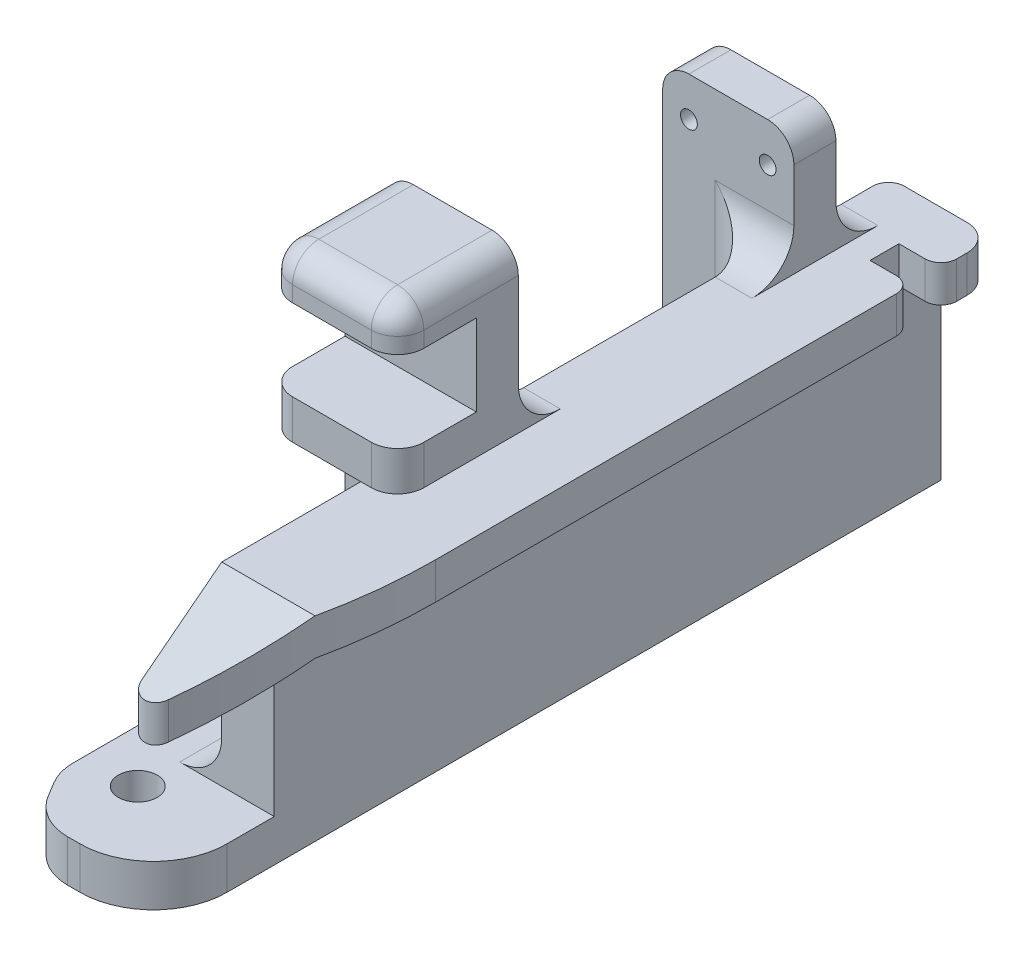
SolidWorks part; units mm, degrees
ref_plane "Front Plane" through (0, 0, 0) normal (0, 0, 1) x (1, 0, 0)
ref_plane "Top Plane" through (0, 0, 0) normal (0, 1, 0) x (1, 0, 0)
ref_plane "Right Plane" through (0, 0, 0) normal (1, 0, 0) x (0, 0, -1)
sketch "Sketch1" plane through (0, 0, 0) normal (0, 1, 0) x (1, 0, 0)
  line L6 (0, 0) -> (0, -140)
  line L13 (0, 0) -> (28, 0)
  line L14 (28, 0) -> (28, -135.9955)
  line L16 (0, -140) -> (6, -150)
  line L17 (6, -150) -> (13.9955, -150)
  circle A1 centre (10, -135) radius 3.7
  arc A2 (13.9955, -150) -> (28, -135.9955) centre (13.9955, -135.9955) ccw
  dimension "D12" = 7.4
  dimension "D2" = 7.9955
  dimension "D3" = 6
  dimension "D4" = 150
  dimension "D5" = 28
  dimension "D6" = 10
  dimension "D7" = 15
  dimension "D8" = 10
extrude "Boss-Extrude1" add sketch "Sketch1" along normal blind 8
fillet "Fillet1" radius 10 2 edges at (0, 4, 140) (6, 4, 150)
sketch "Sketch2" plane through (0, 8, 0) normal (0, 1, 0) x (1, 0, 0)
  line L0 (28, -127) -> (28, 0)
  line L1 (-55, 0) -> (55, 0) construction
  line L2 (28, -135.9955) -> (28, 0) construction
  line L3 (28, 0) -> (18, 0)
  line L4 (18, 0) -> (18, -127)
  line L6 (18, -127) -> (28, -127)
  circle A2 centre (10, -135) radius 3.7 construction
  dimension "D1" = 10
  dimension "D2" = 8
extrude "Boss-Extrude2" add sketch "Sketch2" along normal blind 30 contours L4 L6 L0 L3
sketch "Sketch3" plane through (0, 38, 0) normal (0, 1, 0) x (1, 0, 0)
  line L0 (18, 0) -> (38, 0)
  line L1 (-4.4, 0) -> (4.4, 0) construction
  line L2 (18, 0) -> (18, -127) construction
  line L3 (38, 0) -> (38, -106.265)
  line L4 (18, 0) -> (18, -127)
  line L5 (18, -127) -> (25, -155)
  line L6 (18, 0) -> (18, -127) construction
  line L7 (11.6619, -150) -> (13.9955, -150) construction
  arc A0 (38, -106.265) -> (25, -155) centre (-59.85, -106.265) cw
  circle A4 centre (10, -135) radius 3.7 construction
  dimension "D2" = 5
  dimension "D1" = 20
  dimension "D3" = 15
extrude "Boss-Extrude3" add sketch "Sketch3" along normal blind 7
fillet "Fillet2" radius 3 3 edges at (0, 4, 0) (18, 26.5, 0) (25, 41.5, 155)
sketch "Sketch4" plane through (0, 8, 0) normal (0, 1, 0) x (1, 0, 0)
  line L0 (0, -4.4) -> (0, 4.4) construction
  line L1 (0, -17.0103) -> (18, -17.0103)
  line L2 (0, -17.0103) -> (0, -25.0103)
  line L3 (0, -25.0103) -> (18, -25.0103)
  line L4 (18, -17.0103) -> (18, -25.0103)
  line L5 (18, -3) -> (18, -127) construction
  line L6 (18, -3) -> (18, -127) construction
  line L7 (0, -77.5073) -> (18, -77.5073)
  line L8 (0, -77.5073) -> (0, -85.5073)
  line L9 (0, -85.5073) -> (18, -85.5073)
  line L10 (18, -77.5073) -> (18, -85.5073)
  line L11 (0, -3) -> (0, -137.2302) construction
  line L13 (-101.25, -25.5103) -> (121.25, -25.5103) construction
  line L15 (-101.25, -85.5073) -> (121.25, -85.5073) construction
  dimension "D1" = 8
  dimension "D2" = 8
  dimension "D3" = 0.5
extrude "Boss-Extrude4" add sketch "Sketch4" along normal blind 27
sketch "Sketch5" plane through (0, 35, 0) normal (0, 1, 0) x (1, 0, 0)
  line L1 (0, -17.0103) -> (25, -17.0103)
  line L2 (0, -17.0103) -> (0, -25.0103)
  line L3 (0, -25.0103) -> (25, -25.0103)
  line L4 (25, -17.0103) -> (25, -25.0103)
  line L5 (0, -85.5073) -> (25, -85.5073)
  line L6 (0, -85.5073) -> (0, -77.5073)
  line L7 (0, -77.5073) -> (25, -77.5073)
  line L8 (25, -85.5073) -> (25, -77.5073)
  dimension "D1" = 25
  dimension "D2" = 25
extrude "Boss-Extrude5" add sketch "Sketch5" along normal blind 33
sketch "Sketch6" plane through (0, 68, 0) normal (0, 1, 0) x (1, 0, 0)
  line L0 (0, -85.5073) -> (0, -137.2302) construction
  line L1 (25, -77.5073) -> (0, -77.5073)
  line L2 (25, -77.5073) -> (25, -100.513)
  line L3 (25, -100.513) -> (0, -100.513)
  line L4 (0, -77.5073) -> (0, -100.513)
  dimension "D1" = 23.0057
extrude "Boss-Extrude6" add sketch "Sketch6" along normal blind 8
sketch "Sketch7" plane through (0, 0, 85.5073) normal (0, 0, 1) x (1, 0, 0)
  line L0 (0, 68) -> (0, 8) construction
  line L1 (0, 45) -> (25, 45)
  line L2 (0, 45) -> (0, 52.5)
  line L3 (0, 52.5) -> (25, 52.5)
  line L4 (25, 45) -> (25, 52.5)
  line L5 (25, 68) -> (25, 45) construction
  line L6 (0, 76) -> (25, 76) construction
  line L7 (28.7089, 45) -> (23.0833, 45) construction
  dimension "D1" = 23.5
extrude "Boss-Extrude7" add sketch "Sketch7" along normal blind 15
sketch "Sketch8" plane through (0, 0, 17.0103) normal (0, 0, -1) x (-1, 0, 0)
  line L0 (-25, 68) -> (0, 68) construction
  line L1 (-25, 68) -> (-25, 45) construction
  line L2 (0, 68) -> (0, 8) construction
  circle A0 centre (-20, 60.5) radius 1.6
  circle A1 centre (-5, 60.5) radius 1.6
  dimension "D1" = 3.2
  dimension "D2" = 3.2
  dimension "D3" = 7.5
  dimension "D4" = 5
  dimension "D5" = 5
extrude "Cut-Extrude1" cut sketch "Sketch8" against normal up to next
fillet "Fillet3" radius 8 14 edges at (18.8787, 8, 0.8787) (18, 8, 51.2588) (18, 8, 106.2536) (9, 8, 17.0103) (18, 26.5, 17.0103) (18, 26.5, 25.0103) (9, 8, 25.0103) (9, 8, 77.5073) (18, 26.5, 77.5073) (18, 26.5, 85.5073) (9, 8, 85.5073) (21.5, 45, 25.0103) (21.5, 45, 77.5073) (21.5, 45, 17.0103)
fillet "Fillet4" radius 5 10 edges at (38, 41.5, 0) (25, 68, 21.0103) (25, 76, 89.0101) (0, 76, 89.0101) (0, 68, 21.0103) (12.5, 76, 100.513) (25, 72, 100.513) (0, 72, 100.513) (25, 48.75, 100.5073) (0, 48.75, 100.5073)
sketch "Sketch9" plane through (0, 45, 0) normal (0, 1, 0) x (1, 0, 0)
  line L0 (38, -106.265) -> (38, -5) construction
  line L1 (38, -15.5041) -> (30, -15.5041)
  line L2 (38, -15.5041) -> (38, -10.0041)
  line L3 (38, -10.0041) -> (30, -10.0041)
  line L4 (30, -15.5041) -> (30, -10.0041)
  line L5 (71.25, -15.5041) -> (91.25, -15.5041) construction
  dimension "D1" = 8
  dimension "D2" = 5.5
extrude "Cut-Extrude2" cut sketch "Sketch9" against normal up to next
fillet "Fillet7" radius 3 2 edges at (38, 41.5, 15.5041) (38, 41.5, 10.0041)
sketch "Sketch10" plane through (0, 38, 0) normal (0, -1, 0) x (1, 0, 0)
  line L0 (18, 127) -> (28, 127) construction
  line L1 (18, 127) -> (23.0833, 147.3333) construction
  line L2 (18, 127) -> (28, 127)
  line L3 (18, 127) -> (23.0833, 147.3333)
  line L4 (28, 127) -> (35.7778, 127)
  arc A0 (28.7089, 147.8816) -> (23.0833, 147.3333) centre (25.9938, 146.6057) ccw construction
  arc A1 (38, 106.265) -> (28.7089, 147.8816) centre (-59.85, 106.265) ccw construction
  arc A2 (28.7089, 147.8816) -> (23.0833, 147.3333) centre (25.9938, 146.6057) ccw
  arc A3 (35.7778, 127) -> (28.7089, 147.8816) centre (-59.85, 106.265) ccw
extrude "Boss-Extrude8" add sketch "Sketch10" along normal blind 10
sketch "Sketch11" plane through (18, 0, 0) normal (-1, 0, 0) x (0, 0, 1)
  line L1 (127, 45) -> (127, 28) construction
  line L3 (127, 28) -> (127, 38)
  line L4 (100.5073, 45) -> (127, 45) construction
  line L5 (149.6057, 45) -> (149.6057, 37.5)
  line L6 (149.6057, 28) -> (149.6057, 45) construction
  line L7 (149.6057, 37.5) -> (127, 45)
  line L8 (127, 45) -> (149.6057, 45)
  line L12 (127, 38) -> (149.6057, 30.5)
  line L13 (149.6057, 28) -> (149.6057, 45) construction
  line L15 (127, 28) -> (149.6057, 28)
  line L16 (149.6057, 28) -> (149.6057, 30.5)
  dimension "D1" = 7
  dimension "D2" = 7.5
extrude "Cut-Extrude3" cut sketch "Sketch11" against normal up to vertex (20 mm away) up to point (38, 45, 18.5041)
